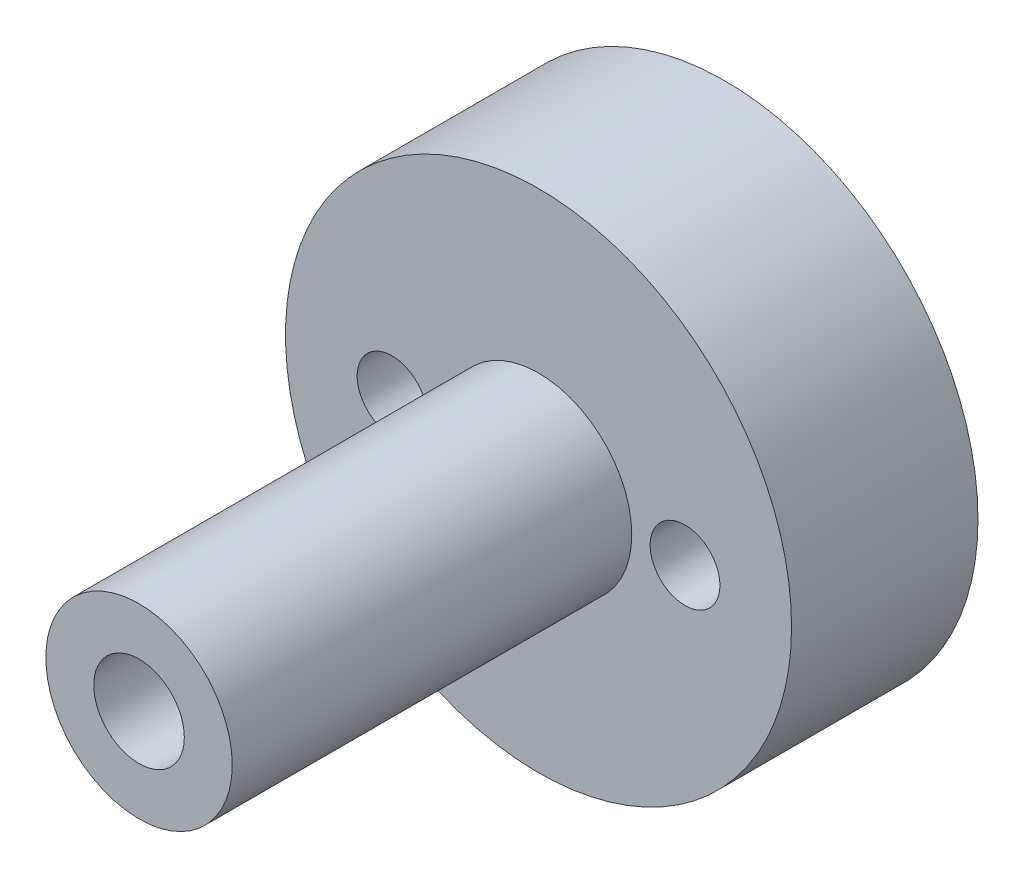
SolidWorks part; units mm, degrees
ref_plane "Front Plane" through (0, 0, 0) normal (0, 0, 1) x (1, 0, 0)
ref_plane "Top Plane" through (0, 0, 0) normal (0, 1, 0) x (1, 0, 0)
ref_plane "Right Plane" through (0, 0, 0) normal (1, 0, 0) x (0, 0, -1)
sketch "Sketch1" plane through (0, 0, 0) normal (0, 0, 1) x (1, 0, 0)
  circle A0 centre (0, 0) radius 7.6
  circle A1 centre (0, 0) radius 9.5
  dimension "D1" = 15.2
  dimension "D2" = 19
extrude "Boss-Extrude1" add sketch "Sketch1" along normal blind 5
sketch "Sketch2" plane through (0, 0, 5) normal (0, 0, 1) x (1, 0, 0)
  circle A0 centre (0, 0) radius 9.5 construction
  circle A1 centre (0, 0) radius 9.5
  circle A2 centre (0, 0) radius 1.31
  dimension "D1" = 2.62
extrude "Boss-Extrude2" add sketch "Sketch2" along normal blind 2
sketch "Sketch3" plane through (0, 0, 7) normal (0, 0, 1) x (1, 0, 0)
  circle A0 centre (-5.5, 0) radius 1.31
  circle A1 centre (5.5, 0) radius 1.31
  circle A2 centre (0, 0) radius 1.31 construction
  circle A3 centre (0, 0) radius 1.7
  circle A4 centre (0, 0) radius 3.5
  dimension "D1" = 5.5
  dimension "D3" = 3.4
  dimension "D4" = 7
  dimension "D2" = 5.5
extrude "Boss-Extrude3" add sketch "Sketch3" along normal blind 15 contours A4 A3 region at (-3.401, 0, 7)
extrude "Cut-Extrude1" cut sketch "Sketch3<3>" against normal through all both and the other way through all contours A0 | A1 region at (-5.5, 0, 7)
sketch "Sketch3<3>" plane through (0, 0, 7) normal (0, 0, 1) x (1, 0, 0) same geometry as "Sketch3"
sketch "Sketch4" plane through (0, 0, 5) normal (0, 0, -1) x (-1, 0, 0)
  circle A0 centre (-5.5, 0) radius 1.31 construction
  circle A1 centre (5.5, 0) radius 1.31 construction
  circle A2 centre (0, 0) radius 1.31 construction
  circle A3 centre (-5.5, 0) radius 1.31
  circle A4 centre (5.5, 0) radius 1.31
  circle A5 centre (0, 0) radius 1.31
  circle A6 centre (5.5, 0) radius 1.81
  circle A7 centre (0, 0) radius 1.81
  circle A8 centre (-5.5, 0) radius 1.81
  dimension "D1" = 0.5
extrude "Boss-Extrude4" add sketch "Sketch4" along normal up to surface (5 mm away) up to face at (9.5, 0, 0)
